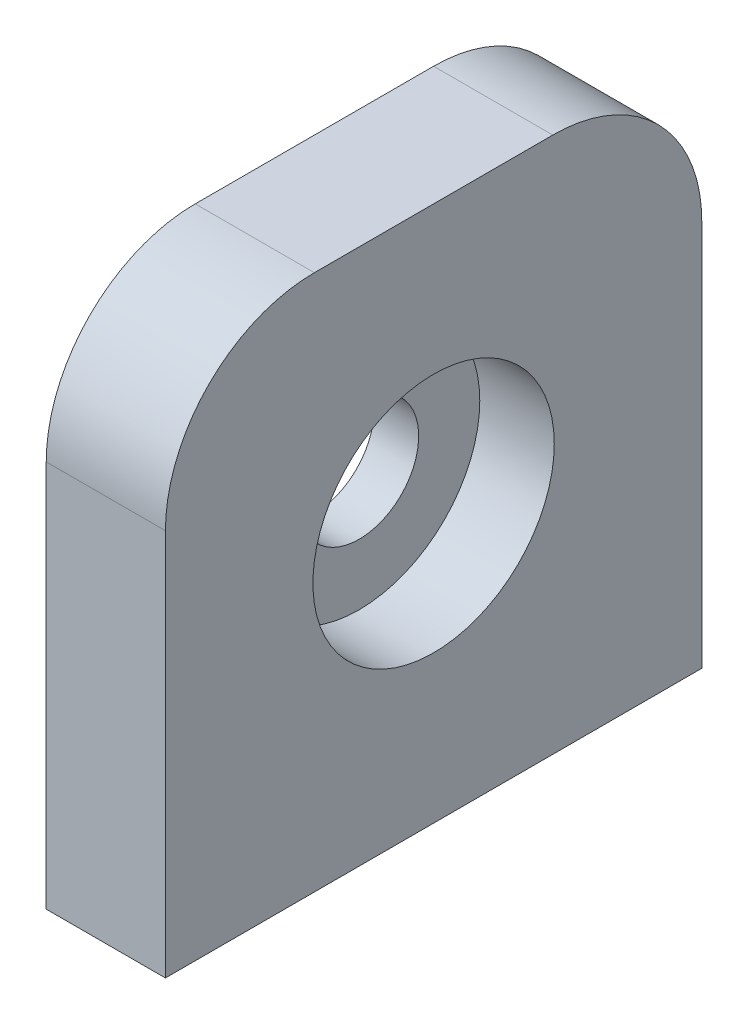
SolidWorks part; units mm, degrees
ref_plane "Plan de face" through (0, 0, 0) normal (0, 0, 1) x (1, 0, 0)
ref_plane "Plan de dessus" through (0, 0, 0) normal (0, 1, 0) x (1, 0, 0)
ref_plane "Plan de droite" through (0, 0, 0) normal (1, 0, 0) x (0, 0, -1)
sketch "Esquisse1" plane through (0, 0, 0) normal (0, 1, 0) x (1, 0, 0)
  line L24 (0, 0) -> (0, 36)
  line L25 (0, 36) -> (8, 36)
  line L26 (8, 36) -> (8, 0)
  line L27 (8, 0) -> (0, 0)
extrude "Boss.-Extru.3" add sketch "Esquisse1" along normal blind 36 contours L27 L26 L25 L24 region at (4, 0, -18)
sketch "Esquisse9" plane through (8, 0, 0) normal (1, 0, 0) x (0, 0, -1)
  line L0 (18, 0) -> (0, 0) construction
  line L2 (18, 0) -> (18, 18) construction
  circle A0 centre (18, 18) radius 8.1
extrude "Enlèv. mat.-Extru.1" cut sketch "Esquisse9" against normal blind 10
sketch "Esquisse10" plane through (0, 0, 0) normal (-1, 0, 0) x (0, 0, 1)
  circle A0 centre (-18, 18) radius 8.1
  circle A1 centre (-18, 18) radius 4
extrude "Boss.-Extru.4" add sketch "Esquisse10" against normal blind 3
sketch "Esquisse13" plane through (0, 0, 0) normal (0, -1, 0) x (1, 0, 0)
  line L0 (0, 0) -> (8, 0) construction
  line L1 (8, 0) -> (8, -8) construction
  line L2 (8, -36) -> (8, 0) construction
  line L3 (8, -8) -> (0, -8) construction
  line L4 (0, 0) -> (0, -36) construction
  line L5 (0, -8) -> (0, 0) construction
  line L6 (0, 0) -> (8, -8) construction
  line L7 (8, -8) -> (8, 0) construction
  line L8 (8, 0) -> (0, -8) construction
  line L9 (0, -36) -> (8, -36) construction
  line L10 (8, -36) -> (8, -28) construction
  line L11 (8, -28) -> (0, -28) construction
  line L12 (0, -28) -> (0, -36) construction
  line L13 (0, -36) -> (8, -28) construction
  line L14 (8, -28) -> (0, -28) construction
  line L15 (0, -28) -> (8, -36) construction
  circle A0 centre (4, -4) radius 2
  circle A1 centre (4, -32) radius 2
extrude "Enlèv. mat.-Extru.2" cut sketch "Esquisse13" against normal blind 15
sketch "Esquisse14" plane through (8, 0, 0) normal (1, 0, 0) x (0, 0, -1)
  line L0 (0, 0) -> (36, 0) construction
  line L1 (36, 0) -> (36, 36) construction
  circle A0 centre (18, 18) radius 6
  circle A1 centre (18, 18) radius 8.1
  dimension "D1" = 16.2
  dimension "D2" = 12
  dimension "D3" = 36
  dimension "D4" = 36
sketch "Esquisse15" plane through (0, 0, 0) normal (-1, 0, 0) x (0, 0, 1)
  line L0 (-36, 36) -> (-36, 0)
  line L1 (-36, 0) -> (0, 0)
  circle A0 centre (-18, 18) radius 6
  dimension "D3" = 12
  dimension "D1" = 36
  dimension "D2" = 36
sketch "Esquisse16" plane through (0, 0, -36) normal (0, 0, -1) x (-1, 0, 0)
  line L0 (-8, 36) -> (0, 36)
  line L1 (0, 36) -> (-8, 36) construction
  line L2 (-8, 36) -> (-8, 0)
  dimension "D1" = 8
  dimension "D2" = 36
fillet "Congé1" radius 10 2 edges at (4, 36, -36) (4, 36, 0)
